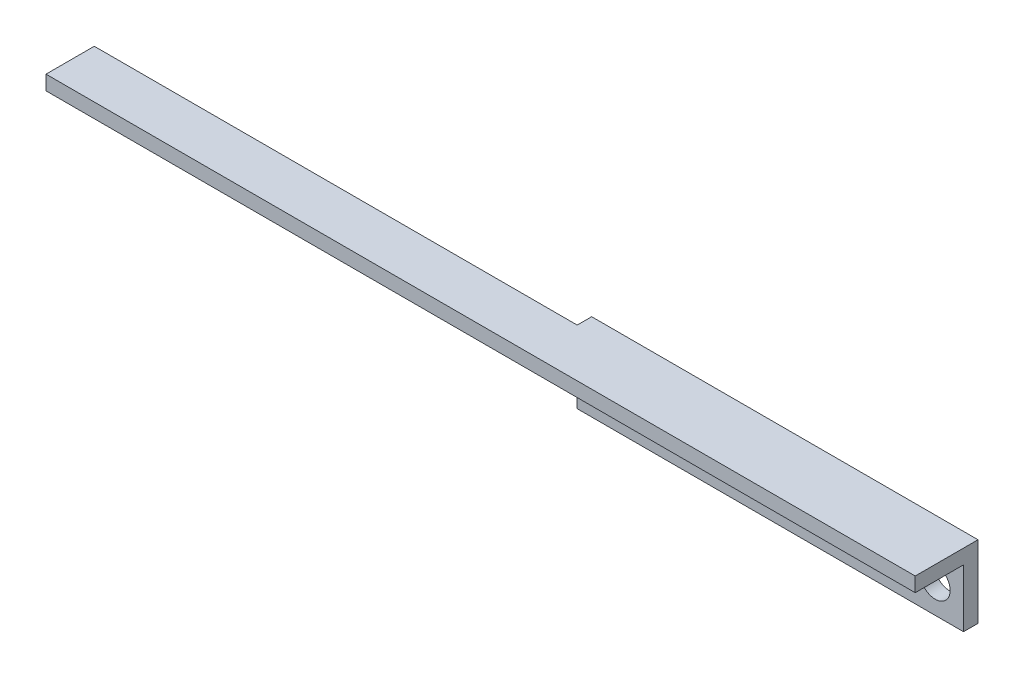
SolidWorks part; units mm, degrees
ref_plane "前视基准面" through (0, 0, 0) normal (0, 0, 1) x (1, 0, 0)
ref_plane "上视基准面" through (0, 0, 0) normal (0, 1, 0) x (1, 0, 0)
ref_plane "右视基准面" through (0, 0, 0) normal (1, 0, 0) x (0, 0, -1)
other "Configuration Table"
sketch "草图1" plane through (0, 0, 0) normal (0, 0, 1) x (1, 0, 0)
  line L1 (20, -3) -> (-20, -3)
  line L2 (20, -3) -> (20, 3)
  line L3 (20, 3) -> (-20, 3)
  line L4 (-20, -3) -> (-20, 3)
  line L5 (20, -3) -> (-20, 3) construction
  line L6 (20, 3) -> (-20, -3) construction
  circle A0 centre (-17.066, 0) radius 1.55
  circle A1 centre (17.066, 0) radius 1.55
  point P0 (0, 0)
  point P6 (-17.066, 0)
  point P7 (17.066, 0)
  dimension "D3" = 3.1
  dimension "D4" = 3.1
  dimension "D1" = 17.066
  dimension "D2" = 17.066
  dimension "D5" = 20
  dimension "D6" = 3
extrude "凸台-拉伸1" add sketch "草图1" along normal blind 1.5
sketch "草图2" plane through (0, 3, 0) normal (0, 1, 0) x (1, 0, 0)
  line L1 (-20, 0) -> (20, 0)
  line L2 (-20, 0) -> (-20, -1.5)
  line L3 (-20, -1.5) -> (20, -1.5)
  line L4 (20, 0) -> (20, -1.5)
extrude "凸台-拉伸2" add sketch "草图2" along normal blind 1.5
sketch "草图3" plane through (0, 0, 1.5) normal (0, 0, 1) x (1, 0, 0)
  line L0 (20, -3) -> (20, 4.5) construction
  line L1 (-20, 4.5) -> (20, 4.5)
  line L2 (-20, 4.5) -> (-20, 3)
  line L3 (-20, 3) -> (20, 3)
  line L4 (20, 4.5) -> (20, 3)
  dimension "D1" = 1.5
sketch "草图4" plane through (0, 0, 0) normal (0, 0, -1) x (-1, 0, 0)
  line L1 (-20, 4.5) -> (20, 4.5)
  line L2 (-20, 4.5) -> (-20, 3)
  line L3 (-20, 3) -> (20, 3)
  line L4 (20, 4.5) -> (20, 3)
extrude "凸台-拉伸4" add sketch "草图4" against normal blind 6.5 contours L1 L4 L3 L2
sketch "草图6" plane through (-20, 0, 0) normal (-1, 0, 0) x (0, 0, 1)
  line L0 (1.5, 4.5) -> (1.5, 3) construction
  line L1 (1.5, 4.5) -> (6.5, 4.5)
  line L2 (1.5, 4.5) -> (1.5, 3)
  line L3 (1.5, 3) -> (6.5, 3)
  line L4 (6.5, 4.5) -> (6.5, 3)
  line L5 (0, 4.5) -> (6.5, 4.5) construction
extrude "凸台-拉伸5" add sketch "草图6" along normal blind 50
